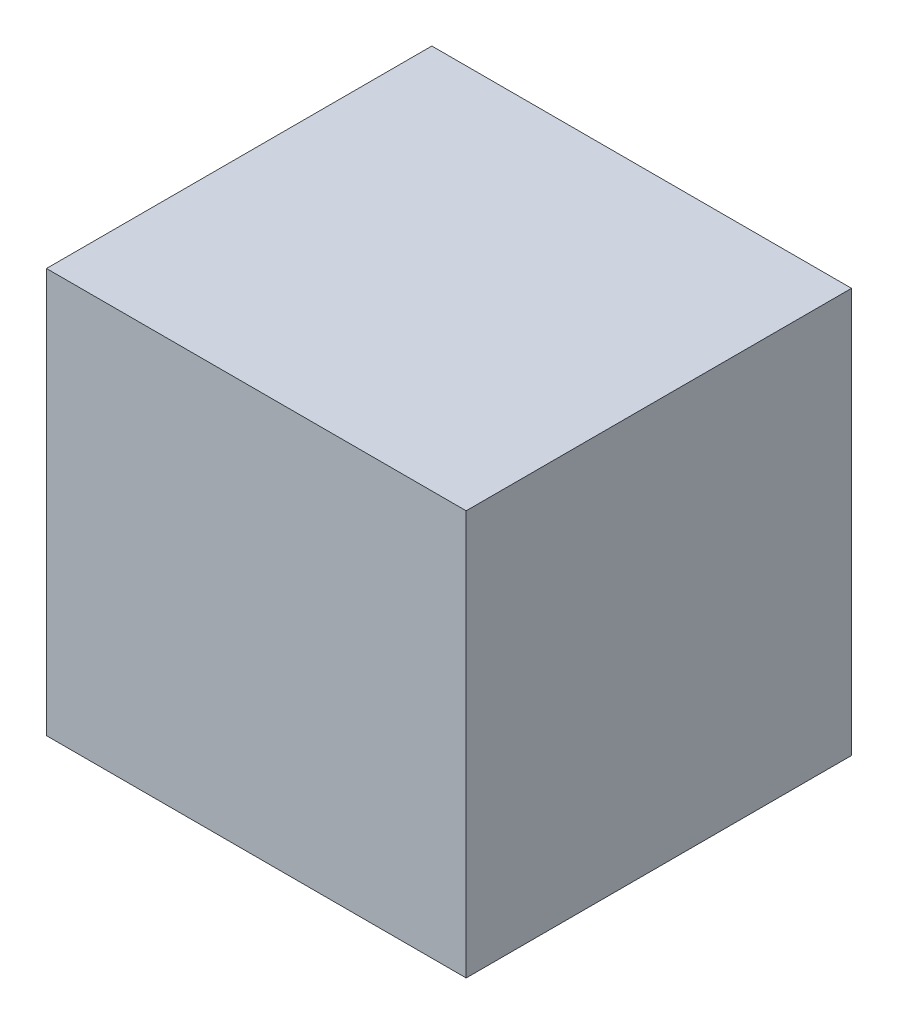
SolidWorks part; units mm, degrees
ref_plane "Piano frontale" through (0, 0, 0) normal (0, 0, 1) x (1, 0, 0)
ref_plane "Piano superiore" through (0, 0, 0) normal (0, 1, 0) x (1, 0, 0)
ref_plane "Piano destro" through (0, 0, 0) normal (1, 0, 0) x (0, 0, -1)
sketch "Schizzo1" plane through (0, 0, 0) normal (0, 0, 1) x (1, 0, 0)
  line L1 (-84.95, -81.9) -> (84.95, -81.9)
  line L2 (-84.95, -81.9) -> (-84.95, 81.9)
  line L3 (-84.95, 81.9) -> (84.95, 81.9)
  line L4 (84.95, -81.9) -> (84.95, 81.9)
  line L5 (-84.95, -81.9) -> (84.95, 81.9) construction
  line L6 (-84.95, 81.9) -> (84.95, -81.9) construction
  point P0 (0, 0)
  dimension "D1" = 169.9
  dimension "D2" = 163.8
extrude "Estrusione-Estrusione1" add sketch "Schizzo1" along normal blind 78 and the other way blind 78
